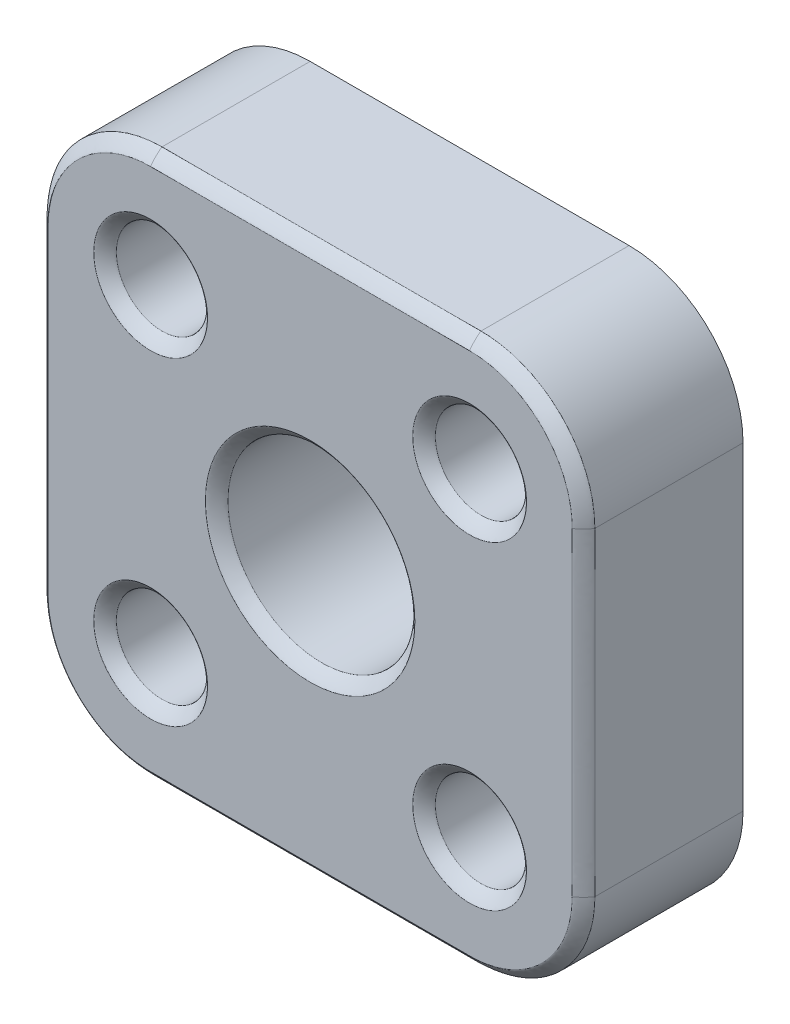
SolidWorks part; units mm, degrees
ref_plane "Plan de face" through (0, 0, 0) normal (0, 0, 1) x (1, 0, 0)
ref_plane "Plan de dessus" through (0, 0, 0) normal (0, 1, 0) x (1, 0, 0)
ref_plane "Plan de droite" through (0, 0, 0) normal (1, 0, 0) x (0, 0, -1)
sketch "Esquisse1" plane through (0, 0, 0) normal (0, 0, 1) x (1, 0, 0)
  line L0 (-7, 7) -> (7, 7) construction
  line L1 (7, -12) -> (-7, -12)
  line L2 (12, -7) -> (12, 7)
  line L3 (7, 12) -> (-7, 12)
  line L4 (-12, -7) -> (-12, 7)
  line L5 (12, -12) -> (-12, 12) construction
  line L6 (12, 12) -> (-12, -12) construction
  line L7 (-7, -7) -> (-7, 7) construction
  arc A0 (-7, -12) -> (-12, -7) centre (-7, -7) cw
  arc A1 (7, -12) -> (12, -7) centre (7, -7) ccw
  arc A2 (12, 7) -> (7, 12) centre (7, 7) ccw
  arc A3 (-7, 12) -> (-12, 7) centre (-7, 7) ccw
  circle A5 centre (-7, 7) radius 2
  circle A6 centre (7, 7) radius 2
  circle A7 centre (7, -7) radius 2
  circle A8 centre (-7, -7) radius 2
  point P0 (0, 0)
  point P18 (12, -12)
  point P20 (7, 7)
  dimension "D2" = 5
  dimension "D3" = 4
  dimension "D1" = 14
  dimension "D6" = 14
  dimension "D7" = 14
  dimension "D4" = 2
  dimension "D5" = 2
extrude "Boss.-Extru.1" add sketch "Esquisse1" along normal blind 7
sketch "Esquisse2" plane through (0, 0, 0) normal (0, 0, -1) x (-1, 0, 0)
  circle A0 centre (0, 0) radius 4.1
  dimension "D1" = 8.2
extrude "Enlèv. mat.-Extru.1" cut sketch "Esquisse2" against normal up to surface (7 mm away) up to face at (0, 0, 7)
fillet "Congé1" radius 0.5 13 edges at (-5, -7, 7) (9, -7, 7) (9, 7, 7) (-5, 7, 7) (-12, 0, 7) (-10.5355, 10.5355, 7) (0, 12, 7) (10.5355, 10.5355, 7) (12, 0, 7) (10.5355, -10.5355, 7) (0, -12, 7) (-10.5355, -10.5355, 7) (-4.1, 0, 7) conic rho 0.1
